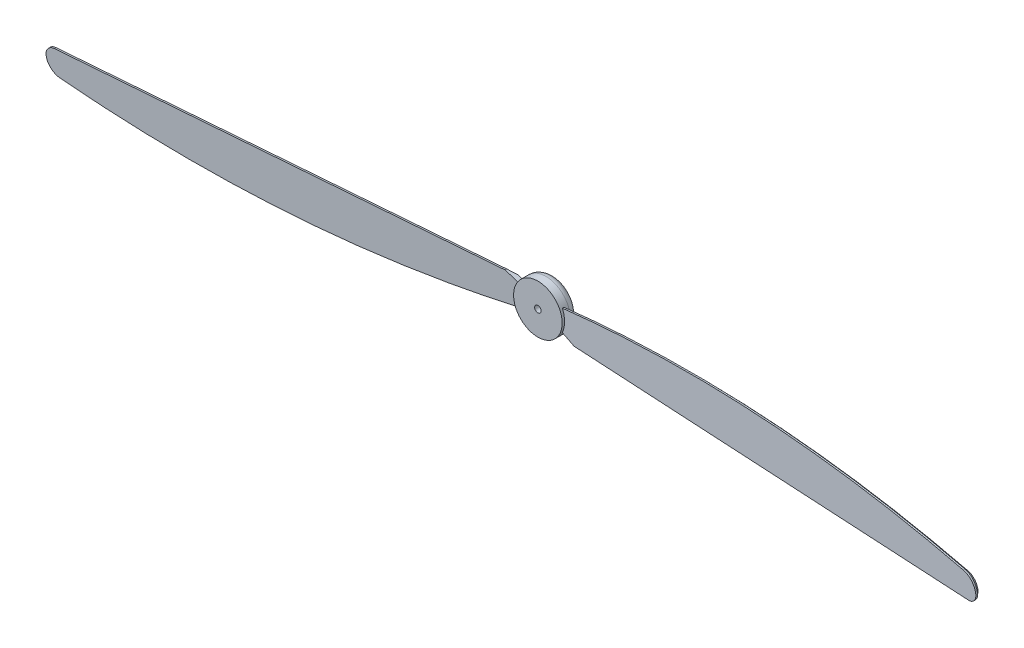
SolidWorks part; units mm, degrees
material "Balsa"
ref_plane "Front Plane" through (0, 0, 0) normal (0, 0, 1) x (1, 0, 0)
ref_plane "Top Plane" through (0, 0, 0) normal (0, 1, 0) x (1, 0, 0)
ref_plane "Right Plane" through (0, 0, 0) normal (1, 0, 0) x (0, 0, -1)
sketch "Sketch1" plane through (0, 0, 0) normal (0, 0, 1) x (1, 0, 0)
  circle A0 centre (0, 0) radius 15
  dimension "D1" = 30
extrude "Boss-Extrude1" add sketch "Sketch1" along normal blind 10
sketch "Sketch2" plane through (0, 0, 0) normal (0, 1, 0) x (1, 0, 0)
  line L1 (-15, -5) -> (15, -7) construction
  line L6 (0, 0) -> (0, -5)
  dimension "D1" = 3
  dimension "D2" = 5
ref_plane "Plane1" through (-0.3982, 0, 5.9735) normal (-0.0665, 0, 0.9978) x (0.9978, 0, 0.0665)
sketch "Sketch3" plane through (-0.3982, 0, 5.9735) normal (-0.0665, 0, 0.9978) x (0.9978, 0, 0.0665)
  line L0 (13.3347, 6.3304) -> (13.3347, -6.3304)
  line L1 (13.3347, -6.3304) -> (21.834, -9.7744)
  line L2 (21.834, -9.7744) -> (288.3347, -6.3304)
  line L3 (288.3347, -6.3304) -> (288.3347, 6.5385)
  spline S0 degree 2 poles (13.3347, 6.3304) (149.7428, 30.1695) (288.3347, 6.5385) knots 0 0 0 1 1 1
  dimension "D1" = 275
extrude "Boss-Extrude2" add sketch "Sketch3" along normal mid plane 3
fillet "Fillet1" radius 10 1 edges at (287.2978, 6.5385, 25.1532)
fillet "Fillet2" radius 5 1 edges at (287.2978, -6.3304, 25.1532)
pattern_circular "CirPattern1" count 2 every 180 about axis through (0, 0, 10) along (0, 0, -1) of "Boss-Extrude2", "Fillet1", "Fillet2" reverse direction yes
chamfer "Chamfer1" distance 2 angle 45 4 edges at (-284.6454, -4.9525, 23.473) (-286.1162, 4.7068, 23.5711) (-151.9651, 8.0845, 14.6277)
chamfer "Chamfer2" distance 2 angle 45 4 edges at (284.6454, 4.9525, 23.473) (286.1162, -4.7068, 23.5711) (151.9651, -8.0845, 14.6277)
sketch "Sketch4" plane through (0, 0, 0) normal (0, 0, -1) x (-1, 0, 0)
  line L0 (15, 0) -> (-15, 0) construction
  circle A0 centre (0, 0) radius 2
  dimension "D1" = 4
extrude "Cut-Extrude1" cut sketch "Sketch4" against normal through all
fillet "Fillet3" radius 5 1 edges at (15, 0, 0)
